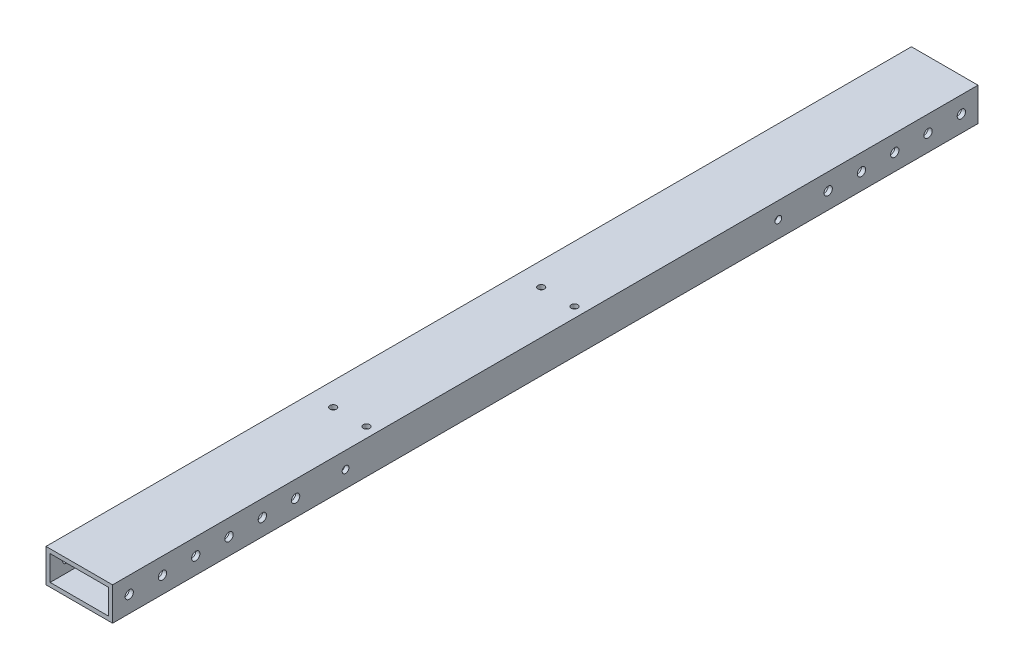
SolidWorks part; units mm, degrees
material "6061 Alloy"
ref_plane "Front Plane" through (0, 0, 0) normal (0, 0, 1) x (1, 0, 0)
ref_plane "Top Plane" through (0, 0, 0) normal (0, 1, 0) x (1, 0, 0)
ref_plane "Right Plane" through (0, 0, 0) normal (1, 0, 0) x (0, 0, -1)
sketch "Sketch1" plane through (0, 0, 0) normal (0, 0, 1) x (1, 0, 0)
  line L0 (-22.225, 9.525) -> (22.225, 9.525)
  line L2 (-25.4, 12.7) -> (25.4, 12.7)
  line L3 (-25.4, 12.7) -> (-25.4, -12.7)
  line L4 (-25.4, -12.7) -> (25.4, -12.7)
  line L5 (25.4, 12.7) -> (25.4, -12.7)
  line L10 (22.225, 9.525) -> (22.225, -9.525)
  line L11 (-22.225, -9.525) -> (22.225, -9.525)
  line L12 (-22.225, 9.525) -> (-22.225, -9.525)
  point P12 (0, 12.7)
  point P14 (25.4, 0)
  dimension "Wall Thickness" = 3.175
  dimension "Outside Width" = 50.8
  dimension "Outside Height" = 25.4
  dimension "Inside Height" = 19.05
  dimension "Inside Width" = 44.45
sketch "Sketch2" plane through (0, 0, 0) normal (1, 0, 0) x (0, 0, -1)
  line L0 (330.2, 0) -> (-330.2, 0)
  point P4 (0, 0)
  point P7 (-330.2, 0)
  point P10 (330.2, 0)
  dimension "Length" = 660.4
sketch "Sketch3" plane through (0, 0, 0) normal (0, 0, 1) x (1, 0, 0)
  line L21 (25.4, 12.7) -> (-25.4, 12.7)
  line L22 (25.4, -12.7) -> (25.4, 12.7)
  line L23 (-25.4, -12.7) -> (25.4, -12.7)
  line L24 (-25.4, 12.7) -> (-25.4, -12.7)
  line L25 (25.4, 12.7) -> (-25.4, 12.7)
  line L26 (25.4, -12.7) -> (25.4, 12.7)
  line L27 (-25.4, -12.7) -> (25.4, -12.7)
  line L28 (-25.4, 12.7) -> (-25.4, -12.7)
  line L29 (22.225, 9.525) -> (-22.225, 9.525)
  line L30 (22.225, -9.525) -> (22.225, 9.525)
  line L31 (-22.225, -9.525) -> (22.225, -9.525)
  line L32 (-22.225, 9.525) -> (-22.225, -9.525)
  line L33 (22.225, 9.525) -> (-22.225, 9.525)
  line L34 (22.225, -9.525) -> (22.225, 9.525)
  line L35 (-22.225, -9.525) -> (22.225, -9.525)
  line L36 (-22.225, 9.525) -> (-22.225, -9.525)
  dimension "D1" = 0
  dimension "D2" = 0
extrude "Boss-Extrude1" add sketch "Sketch3" along normal up to vertex (330.2 mm away) and the other way up to vertex (330.2 mm away) up to point (0, 0, 330.2) other way up to point (0, 0, -330.2)
sketch "Drawing Reference" plane through (0, 0, 0) normal (1, 0, 0) x (0, 0, -1)
  line L0 (-330.2, 0) -> (330.2, 0) construction
  line L1 (0, -12.7) -> (0, 12.7) construction
  line L2 (-330.2, -12.7) -> (330.2, -12.7) construction
  line L5 (-330.2, 12.7) -> (330.2, 12.7) construction
  point P7 (-293.624, 0)
  point P8 (293.624, 0)
  dimension "D1" = 36.576
sketch "Sketch5" plane through (25.4, 0, 0) normal (1, 0, 0) x (0, 0, -1)
  line L2 (-266.7, 0) -> (-241.3, 0)
  line L3 (-241.3, 0) -> (-215.9, 0)
  line L4 (-215.9, 0) -> (-190.5, 0)
  line L5 (-317.5, 0) -> (-330.2, 0)
  line L6 (-330.2, -12.7) -> (-330.2, 12.7) construction
  line L7 (-317.5, 0) -> (-292.1, 0)
  line L8 (-292.1, 0) -> (-266.7, 0)
sketch "Sketch8" plane through (25.4, 0, 0) normal (1, 0, 0) x (0, 0, -1)
  line L0 (330.2, 0) -> (292.1, 0)
  line L1 (330.2, -12.7) -> (330.2, 12.7) construction
  line L2 (292.1, 0) -> (266.7, 0)
  line L3 (266.7, 0) -> (241.3, 0)
  line L4 (241.3, 0) -> (215.9, 0)
  line L5 (330.2, 0) -> (317.5, 0)
hole_wizard "1/4 (0.25) Diameter Hole3" positions "Sketch12" profile "Sketch13" hole size "1/4" standard "ANSI Inch" end condition through all
sketch "Sketch12" plane through (-25.4, 0, 0) normal (-1, 0, 0) x (0, 0, 1)
  point P4 (-317.5, 0)
sketch "Sketch13" plane through (-25.4, 0, -317.5) normal (0, 1, 0) x (0, 0, 1)
  line L0 (0, 0) -> (0, 50.8)
  line L1 (0, 50.8) -> (3.175, 50.8)
  line L2 (3.175, 50.8) -> (3.175, 0)
  line L5 (3.175, 0) -> (0, 0)
  line L11 (0, -6.35) -> (0, 107.95) construction
  dimension "Thru Hole Dia." = 6.35
  dimension "Thru Hole Depth" = 50.8
hole_wizard "1/4 (0.25) Diameter Hole4" positions "Sketch14" profile "Sketch15" hole size "1/4" standard "ANSI Inch" end condition through all
sketch "Sketch14" plane through (-25.4, 0, 0) normal (-1, 0, 0) x (0, 0, 1)
  point P0 (292.1, 0)
  point P3 (317.5, 0)
sketch "Sketch15" plane through (-25.4, 0, 292.1) normal (0, 1, 0) x (0, 0, 1)
  line L0 (0, 0) -> (0, 50.8)
  line L1 (0, 50.8) -> (3.175, 50.8)
  line L2 (3.175, 50.8) -> (3.175, 0)
  line L5 (3.175, 0) -> (0, 0)
  line L11 (0, -6.35) -> (0, 107.95) construction
  dimension "Thru Hole Dia." = 6.35
  dimension "Thru Hole Depth" = 50.8
hole_wizard "1/4 (0.25) Diameter Hole5" positions "Sketch17" profile "Sketch18" hole size "1/4" standard "ANSI Inch" end condition through all
sketch "Sketch17" plane through (25.4, 0, 0) normal (1, 0, 0) x (0, 0, -1)
  point P0 (292.1, 0)
  point P3 (266.7, 0)
sketch "Sketch18" plane through (25.4, 0, -292.1) normal (0, 1, 0) x (0, 0, -1)
  line L0 (0, 0) -> (0, 50.8)
  line L1 (0, 50.8) -> (3.175, 50.8)
  line L2 (3.175, 50.8) -> (3.175, 0)
  line L5 (3.175, 0) -> (0, 0)
  line L11 (0, -6.35) -> (0, 107.95) construction
  dimension "Thru Hole Dia." = 6.35
  dimension "Thru Hole Depth" = 50.8
hole_wizard "1/4 (0.25) Diameter Hole6" positions "Sketch19" profile "Sketch20" hole size "1/4" standard "ANSI Inch" end condition through all
sketch "Sketch19" plane through (25.4, 0, 0) normal (1, 0, 0) x (0, 0, -1)
  point P0 (215.9, 0)
  point P3 (241.3, 0)
sketch "Sketch20" plane through (25.4, 0, -215.9) normal (0, 1, 0) x (0, 0, -1)
  line L0 (0, 0) -> (0, 50.8)
  line L1 (0, 50.8) -> (3.175, 50.8)
  line L2 (3.175, 50.8) -> (3.175, 0)
  line L5 (3.175, 0) -> (0, 0)
  line L11 (0, -6.35) -> (0, 107.95) construction
  dimension "Thru Hole Dia." = 6.35
  dimension "Thru Hole Depth" = 50.8
hole_wizard "1/4 (0.25) Diameter Hole7" positions "Sketch21" profile "Sketch22" hole size "1/4" standard "ANSI Inch" end condition through all
sketch "Sketch21" plane through (25.4, 0, 0) normal (1, 0, 0) x (0, 0, -1)
  point P0 (-190.5, 0)
  point P3 (-215.9, 0)
sketch "Sketch22" plane through (25.4, 0, 190.5) normal (0, 1, 0) x (0, 0, -1)
  line L0 (0, 0) -> (0, 50.8)
  line L1 (0, 50.8) -> (3.175, 50.8)
  line L2 (3.175, 50.8) -> (3.175, 0)
  line L5 (3.175, 0) -> (0, 0)
  line L11 (0, -6.35) -> (0, 107.95) construction
  dimension "Thru Hole Dia." = 6.35
  dimension "Thru Hole Depth" = 50.8
hole_wizard "1/4 (0.25) Diameter Hole8" positions "Sketch23" profile "Sketch24" hole size "1/4" standard "ANSI Inch" end condition through all
sketch "Sketch23" plane through (25.4, 0, 0) normal (1, 0, 0) x (0, 0, -1)
  point P0 (-266.7, 0)
  point P3 (-241.3, 0)
sketch "Sketch24" plane through (25.4, 0, 266.7) normal (0, 1, 0) x (0, 0, -1)
  line L0 (0, 0) -> (0, 50.8)
  line L1 (0, 50.8) -> (3.175, 50.8)
  line L2 (3.175, 50.8) -> (3.175, 0)
  line L5 (3.175, 0) -> (0, 0)
  line L11 (0, -6.35) -> (0, 107.95) construction
  dimension "Thru Hole Dia." = 6.35
  dimension "Thru Hole Depth" = 50.8
sketch "Sketch25" plane through (25.4, 0, 0) normal (1, 0, 0) x (0, 0, -1)
  line L0 (-190.5, 0) -> (-152.4, 0)
  line L1 (215.9, 0) -> (177.8, 0)
hole_wizard "13/64 (0.20313) Diameter Hole1" positions "Sketch26" profile "Sketch27" hole size "13/64" standard "ANSI Inch" end condition through all
sketch "Sketch26" plane through (25.4, 0, 0) normal (1, 0, 0) x (0, 0, -1)
  point P0 (-152.4, 0)
  point P3 (177.8, 0)
sketch "Sketch27" plane through (25.4, 0, 152.4) normal (0, 1, 0) x (0, 0, -1)
  line L0 (0, 0) -> (0, 50.8)
  line L1 (0, 50.8) -> (2.5798, 50.8)
  line L2 (2.5798, 50.8) -> (2.5798, 0)
  line L5 (2.5798, 0) -> (0, 0)
  line L11 (0, -6.35) -> (0, 107.95) construction
  dimension "Thru Hole Dia." = 5.1595
  dimension "Thru Hole Depth" = 50.8
hole_wizard "1/2 (0.5) Diameter Hole1" positions "Sketch33" profile "Sketch34" hole size "1/2" standard "ANSI Inch"
sketch "Sketch33" plane through (-25.4, 0, 0) normal (-1, 0, 0) x (0, 0, 1)
  point P0 (-146.05, 0)
  point P3 (120.65, 0)
sketch "Sketch34" plane through (-25.4, 0, -146.05) normal (0, 1, 0) x (0, 0, 1)
  line L0 (0, 0) -> (0, 10.1655)
  line L1 (0, 10.1655) -> (6.35, 6.35)
  line L2 (6.35, 6.35) -> (6.35, 0)
  line L5 (6.35, 0) -> (0, 0)
  line L10 (0, 10.1655) -> (-6.35, 6.35) construction
  line L11 (0, -6.35) -> (0, 107.95) construction
  dimension "Hole Dia." = 12.7
  dimension "Hole Depth" = 6.35
  dimension "Drill Angle" = 118
sketch "Sketch37" plane through (0, -12.7, 0) normal (0, -1, 0) x (-1, 0, 0)
  line L0 (-25.4, -330.2) -> (-25.4, -128.7188) construction
  line L1 (-25.4, -330.2) -> (-25.4, 330.2) construction
  line L2 (-25.4, -128.7188) -> (-17.6522, -128.7188) construction
  line L3 (-17.6522, -128.7188) -> (7.7478, -128.7188) construction
  line L4 (-25.4, -128.7188) -> (-25.4, 30.0312) construction
  line L5 (-25.4, 30.0312) -> (-17.6522, 30.0312) construction
  line L6 (-17.6522, 30.0312) -> (7.7478, 30.0312) construction
  dimension "D1" = 201.4812
  dimension "D2" = 7.7478
  dimension "D3" = 25.4
  dimension "D4" = 7.7478
  dimension "D5" = 25.4
hole_wizard "#10 Clearance Hole1" positions "Sketch38" profile "Sketch39" hole size "#10" standard "ANSI Inch"
sketch "Sketch38" plane through (0, -12.7, 0) normal (0, -1, 0) x (-1, 0, 0)
  point P0 (7.7478, 30.0312)
  point P3 (-17.6522, 30.0312)
  point P6 (-17.6522, -128.7188)
  point P9 (7.7478, -128.7188)
sketch "Sketch39" plane through (-7.7478, -12.7, -30.0312) normal (1, 0, 0) x (0, 0, -1)
  line L0 (0, 0) -> (0, 26.8957)
  line L1 (0, 26.8957) -> (2.4892, 25.4)
  line L2 (2.4892, 25.4) -> (2.4892, 0)
  line L5 (2.4892, 0) -> (0, 0)
  line L10 (0, 26.8957) -> (-2.4892, 25.4) construction
  line L11 (0, -6.35) -> (0, 107.95) construction
  dimension "Hole Dia." = 4.9784
  dimension "Hole Depth" = 25.4
  dimension "Drill Angle" = 118
equation "\"D1@Drawing Reference\"=\"Outside Width@Sketch1\" * 0.72"
